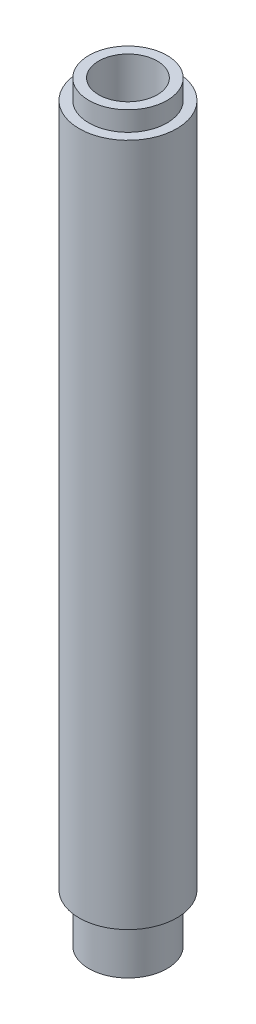
SolidWorks part; units mm, degrees
ref_plane "Front Plane" through (0, 0, 0) normal (0, 0, 1) x (1, 0, 0)
ref_plane "Top Plane" through (0, 0, 0) normal (0, 1, 0) x (1, 0, 0)
ref_plane "Right Plane" through (0, 0, 0) normal (1, 0, 0) x (0, 0, -1)
sketch "Sketch1" plane through (0, 0, 0) normal (0, 1, 0) x (1, 0, 0)
  circle A0 centre (0, 0) radius 12.7
  dimension "D1" = 25.4
extrude "Boss-Extrude1" add sketch "Sketch1" along normal blind 177.8
sketch "Sketch4" plane through (0, 177.8, 0) normal (0, 1, 0) x (1, 0, 0)
  circle A2 centre (0, 0) radius 10.16
  circle A3 centre (0, 0) radius 10.16
  dimension "D1" = 2.54
extrude "Boss-Extrude2" add sketch "Sketch4" along normal blind 5.08
sketch "Sketch5" plane through (0, 182.88, 0) normal (0, 1, 0) x (1, 0, 0)
  circle A0 centre (0, 0) radius 10.16 construction
  circle A1 centre (0, 0) radius 10.16 construction
  circle A2 centre (0, 0) radius 7.62
  dimension "D1" = 2.54
extrude "Cut-Extrude1" cut sketch "Sketch5" against normal through all
sketch "Sketch6" plane through (0, 0, 0) normal (0, -1, 0) x (1, 0, 0)
  circle A0 centre (0, 0) radius 10.16
  circle A1 centre (0, 0) radius 7.62 construction
  circle A2 centre (0, 0) radius 7.62
  dimension "D1" = 20.32
extrude "Boss-Extrude3" add sketch "Sketch6" along normal blind 12.7
sketch "Sketch7" plane through (0, -12.7, 0) normal (0, -1, 0) x (1, 0, 0)
  circle A0 centre (0, 0) radius 12.7 construction
  circle A1 centre (0, 0) radius 12.7
